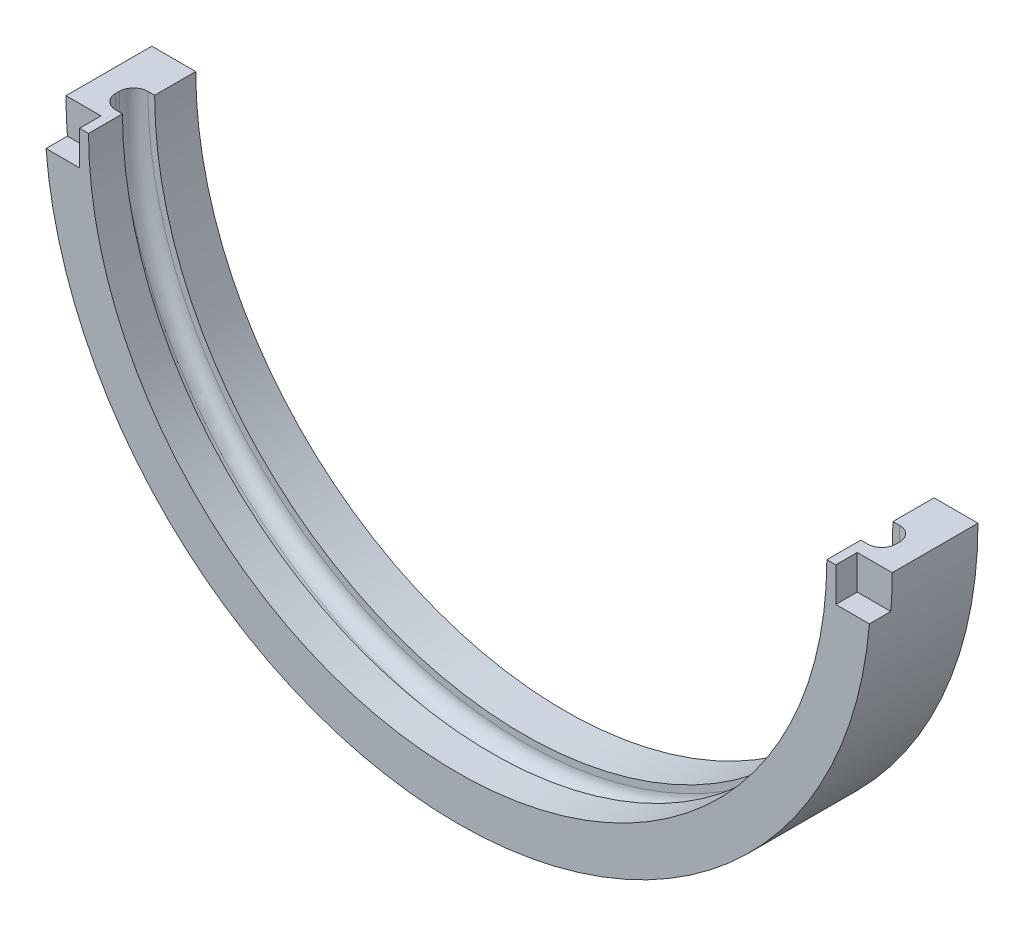
SolidWorks part; units mm, degrees
ref_plane "Front Plane" through (0, 0, 0) normal (0, 0, 1) x (1, 0, 0)
ref_plane "Top Plane" through (0, 0, 0) normal (0, 1, 0) x (1, 0, 0)
ref_plane "Right Plane" through (0, 0, 0) normal (1, 0, 0) x (0, 0, -1)
sketch "Sketch1" plane through (0, 0, 0) normal (0, 0, 1) x (1, 0, 0)
  line L0 (-69.342, 73.406) -> (-73.406, 73.406)
  line L1 (69.342, 73.406) -> (73.406, 73.406)
  circle A0 centre (0, 73.406) radius 73.406
  circle A1 centre (0, 73.406) radius 69.342
  dimension "D1" = 146.812
  dimension "D2" = 138.684
extrude "Boss-Extrude1" add sketch "Sketch1" along normal blind 5.715 contours A1 L0 A0 L1 region at (0, 2.4226, 0)
sketch "Sketch3" plane through (0, 0, 5.715) normal (0, 0, 1) x (1, 0, 0)
  line L0 (-65.5955, 73.406) -> (-73.406, 73.406)
  line L1 (65.5955, 73.406) -> (73.406, 73.406)
  circle A0 centre (0, 73.406) radius 73.406
  circle A1 centre (0, 73.406) radius 65.5955
  arc M3 (69.342, 73.406) -> (-69.342, 73.406) centre (0, 73.406) cw
  line M4 (-69.342, 73.406) -> (-73.406, 73.406)
  arc M5 (-73.406, 73.406) -> (73.406, 73.406) centre (0, 73.406) ccw
  line M6 (73.406, 73.406) -> (69.342, 73.406)
  dimension "D1" = 131.191
extrude "Boss-Extrude2" add sketch "Sketch3" along normal blind 6.0325 contours A1 L0 L1 M3 | M6 M3 M4 M5 region at (0, 6.26, 5.715) region at (0, 2.4226, 5.715)
sketch "Sketch4" plane through (0, 0, 0) normal (0, 0, -1) x (-1, 0, 0)
  line L0 (-65.5955, 73.406) -> (-73.406, 73.406)
  line L1 (65.5955, 73.406) -> (73.406, 73.406)
  circle A0 centre (0, 73.406) radius 73.406
  circle A1 centre (0, 73.406) radius 65.5955
  arc M3 (69.342, 73.406) -> (-69.342, 73.406) centre (0, 73.406) cw
  line M4 (-69.342, 73.406) -> (-73.406, 73.406)
  arc M5 (-73.406, 73.406) -> (73.406, 73.406) centre (0, 73.406) ccw
  line M6 (73.406, 73.406) -> (69.342, 73.406)
extrude "Boss-Extrude3" add sketch "Sketch4" along normal blind 7.3025 contours A1 L0 L1 M3 | M6 M3 M4 M5 region at (0, 6.26, 0) region at (0, 2.4226, 0)
fillet "Fillet1" radius 2.54 2 edges at (0, 4.064, 5.715) (0, 4.064, 0)
sketch "Sketch5" plane through (0, 0, 0) normal (0, 1, 0) x (1, 0, 0)
  line L0 (64.2819, -2.8575) -> (-64.2819, -2.8575) construction
  circle A0 centre (0, -2.8575) radius 1.524
  dimension "D1" = 3.048
extrude "Cut-Extrude1" [suppressed] cut sketch "Sketch5" along normal blind 6.35
sketch "Sketch6" plane through (0, 0, 11.7475) normal (0, 0, 1) x (1, 0, 0)
  line L0 (-65.5955, 73.406) -> (-73.406, 73.406) construction
  line L1 (-67.1839, 73.406) -> (-73.8294, 73.406)
  line L2 (-67.1839, 73.406) -> (-67.1839, 67.31)
  line L3 (-67.1839, 67.31) -> (-73.8294, 67.31)
  line L4 (-73.8294, 73.406) -> (-73.8294, 67.31)
  line L5 (0, 10.7538) -> (0, 95.14) construction
  line L18 (67.1839, 67.31) -> (73.8294, 67.31)
  line L19 (73.8294, 73.406) -> (73.8294, 67.31)
  line L20 (67.1839, 73.406) -> (73.8294, 73.406)
  line L21 (67.1839, 73.406) -> (67.1839, 67.31)
  dimension "D1" = 6.096
extrude "Cut-Extrude5" cut sketch "Sketch6" against normal blind 3.81
